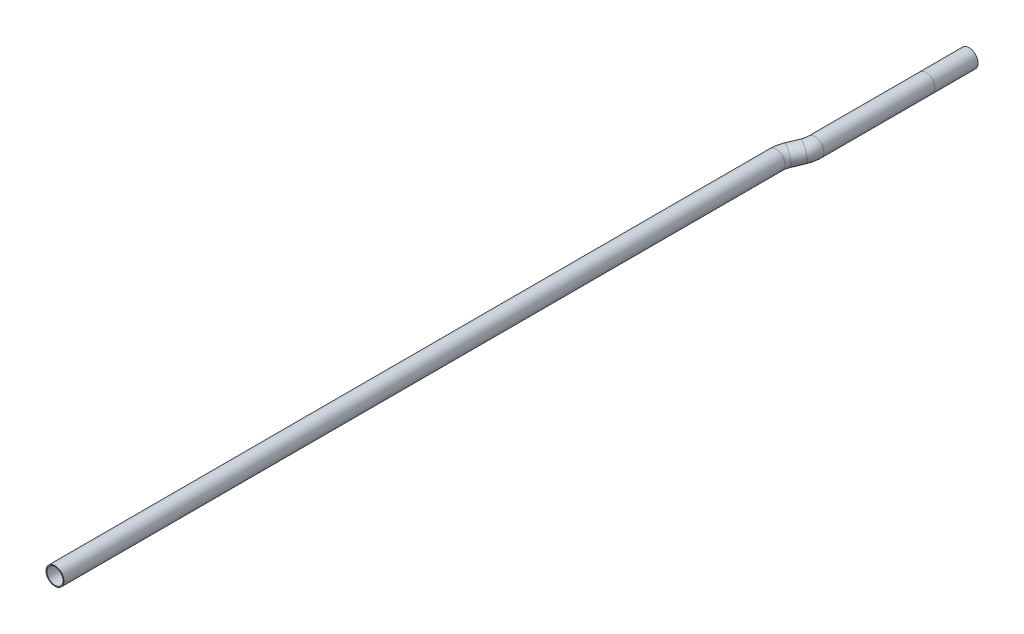
SolidWorks part; units mm, degrees
material "6061 Alloy"
ref_plane "Front Plane" through (0, 0, 0) normal (0, 0, 1) x (1, 0, 0)
ref_plane "Top Plane" through (0, 0, 0) normal (0, 1, 0) x (1, 0, 0)
ref_plane "Right Plane" through (0, 0, 0) normal (1, 0, 0) x (0, 0, -1)
sketch "Sketch1" plane through (0, 0, 0) normal (0, 0, 1) x (1, 0, 0)
  line L0 (0, 0) -> (3.7368, 0.7433) construction
  circle A0 centre (3.7368, 0.7433) radius 2.8575
  circle A1 centre (3.7368, 0.7433) radius 3.175
  dimension "D1" = 6.35
  dimension "D2" = 0.3175
ref_axis "Axis1" through (3.7368, 0.7433, -94.0391) along (0, 0, 1)
ref_plane "Plane1" through (0, 0, 0) normal (-0.1951, 0.9808, 0) x (0, 0, 1)
sketch "Sketch2" plane through (0, 0, 0) normal (-0.1951, 0.9808, 0) x (0, 0, 1)
  line L0 (0, 0) -> (0, 3.81) construction
  line L1 (0, 3.81) -> (-12.7, 3.81)
  line L2 (0, 3.81) -> (2.54, 3.81)
  line L3 (7.0301, 5.6699) -> (12.2004, 10.8401) construction
  line L4 (16.6905, 12.7) -> (33.8547, 12.7) construction
  line L5 (38.3448, 10.8401) -> (47.3251, 1.8599) construction
  line L6 (51.8152, 0) -> (307.0852, 0)
  line L8 (0, 0) -> (36.3164, 0) construction
  line L9 (286.7652, 3.175) -> (286.7652, -3.175) construction
  line L10 (72.1352, 3.175) -> (72.1352, -3.175) construction
  line L11 (0, 0.635) -> (0, 6.985) construction
  line L12 (2.54, 3.81) -> (41.8131, 3.81)
  line L13 (44.9881, 2.9593) -> (48.6402, 0.8507)
  arc A0 (2.54, 3.81) -> (7.0301, 5.6699) centre (2.54, 10.16) ccw construction
  arc A1 (12.2004, 10.8401) -> (16.6905, 12.7) centre (16.6905, 6.35) cw construction
  arc A2 (33.8547, 12.7) -> (38.3448, 10.8401) centre (33.8547, 6.35) cw construction
  arc A3 (47.3251, 1.8599) -> (51.8152, 0) centre (51.8152, 6.35) ccw construction
  arc A4 (41.8131, 3.81) -> (44.9881, 2.9593) centre (41.8131, -2.54) cw
  arc A5 (48.6402, 0.8507) -> (51.8152, 0) centre (51.8152, 6.35) ccw
  dimension "D3" = 6.35
  dimension "D4" = 6.35
  dimension "D5" = 6.35
  dimension "D6" = 6.35
  dimension "D13" = 6.35
  dimension "D14" = 6.35
  dimension "D1" = 3.81
  dimension "D2" = 12.7
  dimension "D7" = 20.32
  dimension "D8" = 12.7
  dimension "D9" = 135
  dimension "D10" = 135
  dimension "D11" = 20.32
  dimension "D12" = 2.54
  dimension "D15" = 30
sweep "Sweep1" add profiles "Sketch1" path "Sketch2"
